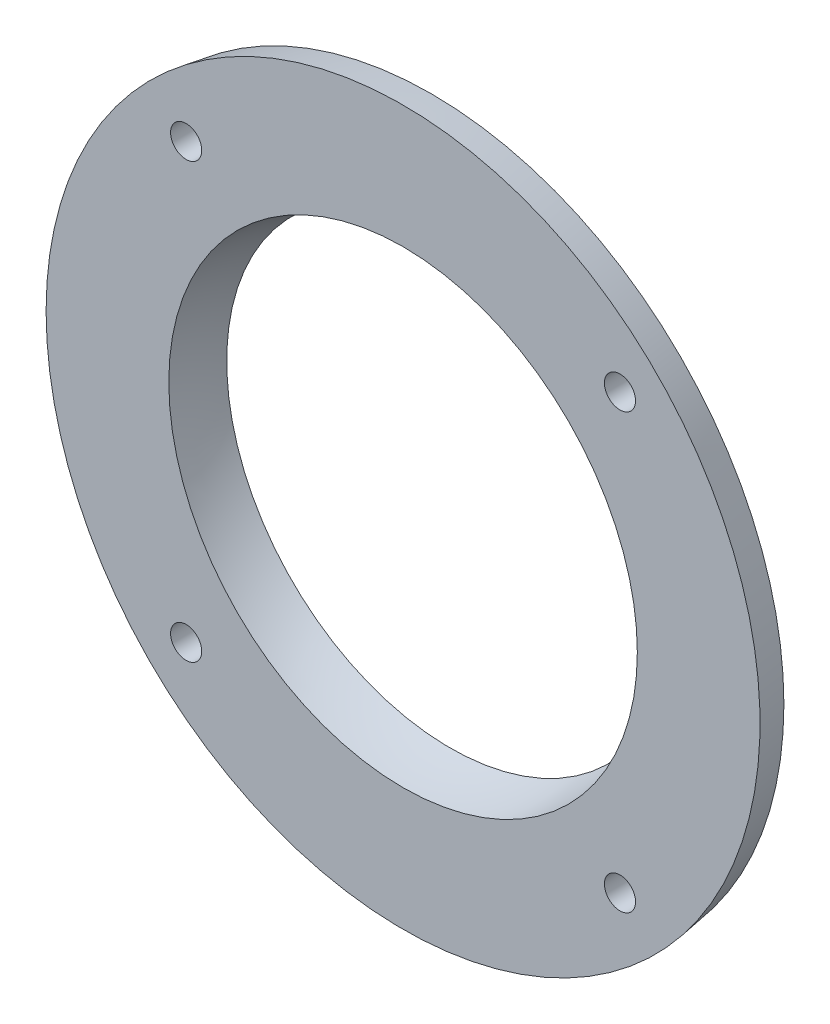
SolidWorks part; units mm, degrees
ref_plane "Front Plane" through (0, 0, 0) normal (0, 0, 1) x (1, 0, 0)
ref_plane "Top Plane" through (0, 0, 0) normal (0, 1, 0) x (1, 0, 0)
ref_plane "Right Plane" through (0, 0, 0) normal (1, 0, 0) x (0, 0, -1)
sketch "Sketch1" plane through (0, 0, 0) normal (0, 1, 0) x (1, 0, 0)
  line L0 (-42.821, 0) -> (37.8193, 0) construction
  line L1 (0, 42.3407) -> (0, -38.2321) construction
  line L7 (0, -3) -> (-42.821, -3) construction
  line L8 (24.8193, 0) -> (37.8193, 0)
  line L12 (27.3496, 3) -> (37.3486, 3)
  line L13 (37.8193, 0) -> (37.8193, 3) construction
  line L14 (23.6854, 5) -> (26.8328, 5)
  line L15 (37.8193, 3) -> (32.7183, 2.8693) construction
  line L16 (27.3496, 3) -> (29.7212, 3) construction
  line L17 (29.7212, 3) -> (29.7212, 3) construction
  line L18 (29.7212, 3) -> (29.7212, 3) construction
  arc A3 (25, -3) -> (-25, -3) centre (0, -3) ccw construction
  arc A4 (24, -3) -> (-24, -3) centre (0, -3) ccw construction
  arc A5 (23.6854, 5) -> (24.8193, 0) centre (0, -3) cw
  arc A6 (26.8328, 5) -> (27.3496, 3) centre (0, -3) cw
  arc A7 (26.5277, 5.96) -> (27.3496, 3) centre (0, -3) cw construction
  arc A8 (37.8275, -3) -> (0, 34.8275) centre (0, -3) ccw construction
  arc A9 (-37.7083, 0) -> (-37.8275, -3) centre (0, -3) ccw construction
  arc A10 (37.8193, 0) -> (37.3486, 3) centre (-373.5717, -63.0137) ccw
  dimension "D1" = 13
  dimension "D6" = 2
  dimension "D4" = 37.8275
  dimension "D2" = 3
  dimension "D3" = 25
  dimension "D5" = 3
revolve "Revolve1" add sketch "Sketch1" angle 360 about L1
sketch "Sketch8" plane through (0, 0, -3) normal (0, 0, -1) x (-1, 0, 0)
  line L0 (0, 0) -> (10.5243, 10.5243) construction
  point P1 (22.981, 22.981)
  dimension "D1" = 32.5
hole_wizard "Tap Drill for M4x0.7 Tap2" positions "Sketch12" profile "Sketch13" hole size "M4x0.7" standard "ANSI Metric" end condition through all
sketch "Sketch12" plane through (0, 0, -3) normal (0, 0, -1) x (-1, 0, 0)
  point P10 (22.981, 22.981)
sketch "Sketch13" plane through (-22.981, 22.981, -3) normal (1, 0, 0) x (0, 1, 0)
  line L0 (0, 0) -> (0, 3)
  line L1 (0, 3) -> (1.65, 3)
  line L2 (1.65, 3) -> (1.65, 0.025)
  line L3 (1.65, 0.025) -> (1.675, 0)
  line L5 (1.675, 0) -> (0, 0)
  line L6 (-1.65, 0.025) -> (-1.675, 0) construction
  line L11 (0, -6.35) -> (0, 107.95) construction
  dimension "Thru Hole Dia." = 3.3
  dimension "Thru Hole Depth" = 3
  dimension "Near C'Sink Dia." = 3.35
  dimension "Near C'Sink Angle" = 90
pattern_circular "CirPattern2" count 4 over 360 about axis through (0, 0, -3) along (0, 0, -1) of "Tap Drill for M4x0.7 Tap2"
fillet "Fillet1" radius 7 1 edges at (-27.3496, 0, -3)
sketch "Sketch16" plane through (0, 0, -3) normal (0, 0, -1) x (-1, 0, 0)
  circle A0 centre (-22.981, -22.981) radius 1.65 construction
  circle A1 centre (-22.981, 22.981) radius 1.65 construction
  circle A2 centre (22.981, 22.981) radius 1.65 construction
  circle A3 centre (22.981, -22.981) radius 1.65 construction
  circle A4 centre (-22.981, -22.981) radius 1.65 construction
  circle A5 centre (-22.981, 22.981) radius 1.65 construction
  circle A6 centre (22.981, 22.981) radius 1.65 construction
  circle A7 centre (22.981, -22.981) radius 1.65 construction
  circle A8 centre (-22.981, -22.981) radius 3.6
  circle A9 centre (-22.981, 22.981) radius 3.6
  circle A10 centre (22.981, 22.981) radius 3.6
  circle A11 centre (22.981, -22.981) radius 3.6
  dimension "D1" = 7.2
extrude "Cut-Extrude1" cut sketch "Sketch16" along normal blind 10
